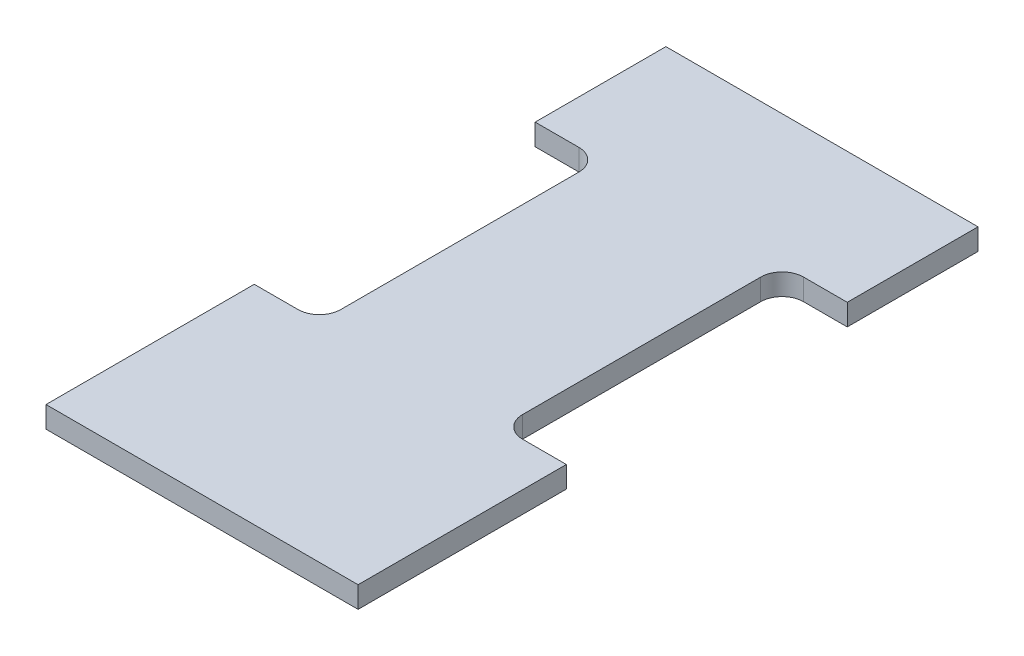
SolidWorks part; units mm, degrees
ref_plane "Front Plane" through (0, 0, 0) normal (0, 0, 1) x (1, 0, 0)
ref_plane "Top Plane" through (0, 0, 0) normal (0, 1, 0) x (1, 0, 0)
ref_plane "Right Plane" through (0, 0, 0) normal (1, 0, 0) x (0, 0, -1)
sketch "Sketch1" plane through (0, 0, 0) normal (0, 1, 0) x (1, 0, 0)
  line L0 (0, 72.5) -> (0, -72.5) construction
  line L1 (-36.5, -72.5) -> (36.5, -72.5)
  line L2 (-36.5, -72.5) -> (-36.5, 72.5) construction
  line L3 (-36.5, 72.5) -> (36.5, 72.5)
  line L4 (36.5, -72.5) -> (36.5, 72.5) construction
  line L5 (-36.5, -72.5) -> (36.5, 72.5) construction
  line L6 (-36.5, 72.5) -> (36.5, -72.5) construction
  line L7 (-36.5, 41.9171) -> (-26.2657, 41.9171)
  line L8 (-21.2657, 36.9171) -> (-21.2657, -18.7867)
  line L9 (-26.2657, -23.7867) -> (-36.5, -23.7867)
  line L10 (-36.5, -23.7867) -> (-36.5, -72.5)
  line L11 (-36.5, 41.9171) -> (-36.5, 72.5)
  line L12 (36.5, -23.7867) -> (36.5, -72.5)
  line L13 (26.2657, -23.7867) -> (36.5, -23.7867)
  line L14 (21.2657, 36.9171) -> (21.2657, -18.7867)
  line L15 (36.5, 41.9171) -> (26.2657, 41.9171)
  line L16 (36.5, 41.9171) -> (36.5, 72.5)
  arc A12 (26.2657, -23.7867) -> (21.2657, -18.7867) centre (26.2657, -18.7867) cw
  arc A13 (21.2657, 36.9171) -> (26.2657, 41.9171) centre (26.2657, 36.9171) cw
  arc A14 (-21.2657, -18.7867) -> (-26.2657, -23.7867) centre (-26.2657, -18.7867) cw
  arc A15 (-26.2657, 41.9171) -> (-21.2657, 36.9171) centre (-26.2657, 36.9171) cw
  point P0 (0, 0)
  point P40 (21.2657, -23.7867)
  point P43 (21.2657, 41.9171)
  point P46 (-21.2657, -23.7867)
  point P49 (-21.2657, 41.9171)
  dimension "D5" = 5
  dimension "D1" = 73
  dimension "D2" = 145
extrude "Boss-Extrude1" add sketch "Sketch1" along normal blind 5
